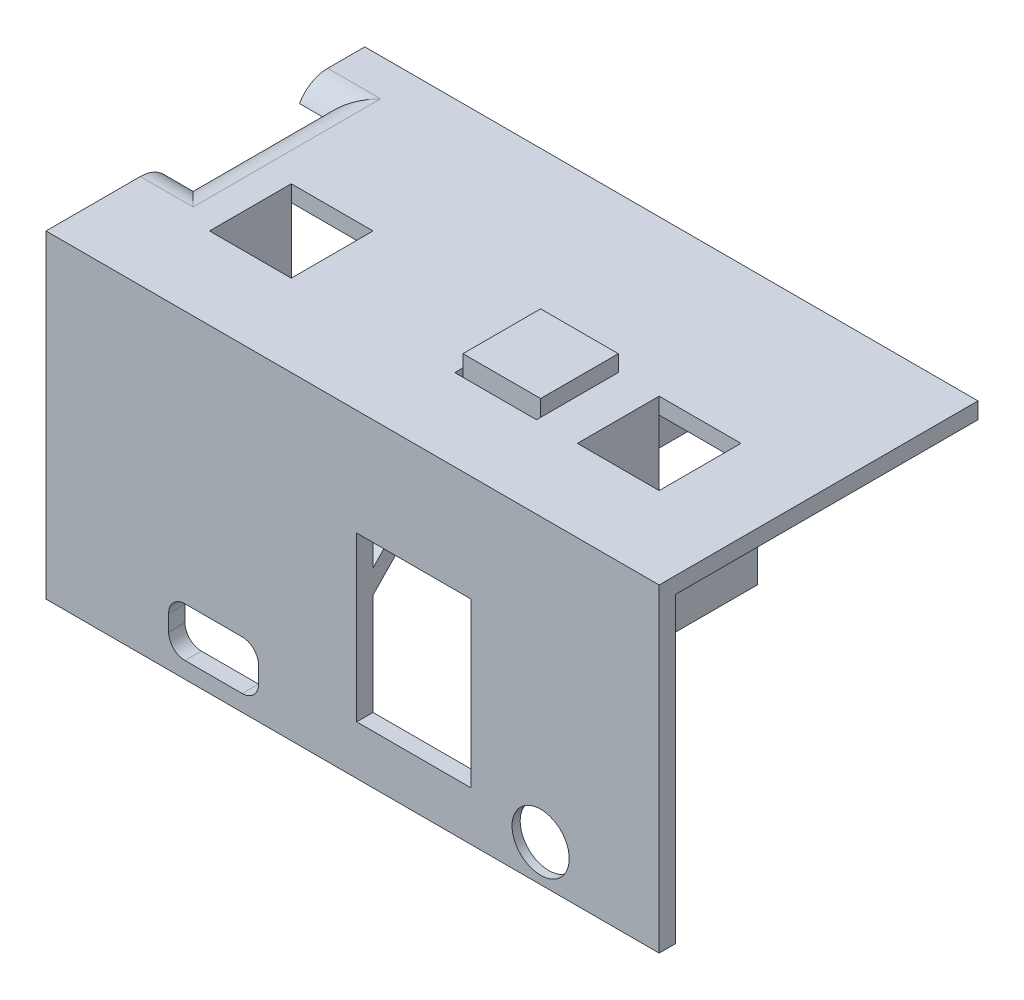
SolidWorks part; units mm, degrees
ref_plane "Front Plane" through (0, 0, 0) normal (0, 0, 1) x (1, 0, 0)
ref_plane "Top Plane" through (0, 0, 0) normal (0, 1, 0) x (1, 0, 0)
ref_plane "Right Plane" through (0, 0, 0) normal (1, 0, 0) x (0, 0, -1)
sketch "Sketch1" plane through (0, 0, 0) normal (0, 0, 1) x (1, 0, 0)
  line L1 (-37.5, 19.5) -> (37.5, 19.5)
  line L2 (-37.5, 19.5) -> (-37.5, -19.5)
  line L3 (-37.5, -19.5) -> (37.5, -19.5)
  line L4 (37.5, 19.5) -> (37.5, -19.5)
  point P4 (37.5, 0)
  point P6 (0, -19.5)
  dimension "D1" = 75
  dimension "D2" = 39
extrude "Boss-Extrude1" add sketch "Sketch1" along normal blind 2
sketch "Sketch2" plane through (0, 0, 0) normal (0, 0, -1) x (-1, 0, 0)
  line L0 (37.5, 19.5) -> (37.5, -19.5) construction
  line L1 (-37.5, 19.5) -> (37.5, 19.5)
  line L2 (-37.5, 19.5) -> (-37.5, 17.5)
  line L3 (-37.5, 17.5) -> (37.5, 17.5)
  line L4 (37.5, 19.5) -> (37.5, 17.5)
  dimension "D1" = 2
extrude "Boss-Extrude2" add sketch "Sketch2" along normal blind 38
sketch "Sketch4" plane through (0, 0, 2) normal (0, 0, 1) x (1, 0, 0)
  line L0 (37.5, -10.5) -> (28.5, -10.5) construction
  line L1 (37.5, -19.5) -> (37.5, 19.5) construction
  line L2 (28.5, -10.5) -> (28.5, -19.5) construction
  line L3 (-37.5, -19.5) -> (37.5, -19.5) construction
  line L4 (23, -19.5) -> (23, -15) construction
  line L5 (-37.5, 19.5) -> (-37.5, -19.5) construction
  line L6 (37.5, 19.5) -> (-37.5, 19.5) construction
  line L7 (-22.5, -11.5) -> (-11.5, -11.5)
  line L8 (-22.5, -11.5) -> (-22.5, -17.5)
  line L9 (-22.5, -17.5) -> (-11.5, -17.5)
  line L10 (-11.5, -11.5) -> (-11.5, -17.5)
  circle A0 centre (23, -15) radius 3.5
  circle A1 centre (23, 4.5) radius 2.25
  dimension "D5" = 7
  dimension "D10" = 4.5
  dimension "D1" = 9
  dimension "D2" = 9
  dimension "D3" = 4.5
  dimension "D4" = 14.5
  dimension "D6" = 15
  dimension "D7" = 49
  dimension "D8" = 2
  dimension "D9" = 6
  dimension "D11" = 15
extrude "Cut-Extrude1" cut sketch "Sketch4" against normal up to surface (2 mm away) up to face at (0, -1, 0)
sketch "Sketch6" plane through (0, 19.5, 0) normal (0, 1, 0) x (1, 0, 0)
  line L0 (37.5, -2) -> (37.5, 38) construction
  line L1 (2.5, 18) -> (12.5, 18)
  line L2 (2.5, 18) -> (2.5, 8)
  line L3 (2.5, 8) -> (12.5, 8)
  line L4 (12.5, 18) -> (12.5, 8)
  line L5 (17.5, 18) -> (27.5, 18)
  line L6 (17.5, 18) -> (17.5, 8)
  line L7 (17.5, 8) -> (27.5, 8)
  line L8 (27.5, 18) -> (27.5, 8)
  line L9 (37.5, -2) -> (-37.5, -2) construction
  line L10 (-37.5, -2) -> (-37.5, 38) construction
  line L11 (-27.5, 18) -> (-17.5, 18)
  line L12 (-27.5, 18) -> (-27.5, 8)
  line L13 (-27.5, 8) -> (-17.5, 8)
  line L14 (-17.5, 18) -> (-17.5, 8)
  dimension "D1" = 10
  dimension "D2" = 10
  dimension "D3" = 5
  dimension "D4" = 10
  dimension "D5" = 10
  dimension "D6" = 10
  dimension "D7" = 10
  dimension "D8" = 10
  dimension "D9" = 10
  dimension "D10" = 10
  dimension "D11" = 10
  dimension "D12" = 10
extrude "Cut-Extrude2" cut sketch "Sketch6" against normal up to surface (2 mm away) up to face at (0, 17.5, -19)
sketch "Sketch7" plane through (0, 17.5, 0) normal (0, -1, 0) x (1, 0, 0)
  line L0 (12.5, -18) -> (12.5, -8) construction
  line L2 (17.5, -8) -> (17.5, -18)
  line L3 (17.5, -18) -> (15.5, -18)
  line L4 (15.5, -8) -> (15.5, -18)
  line L6 (27.5, -8) -> (27.5, -18)
  line L7 (27.5, -18) -> (29.5, -18)
  line L8 (29.5, -8) -> (29.5, -18)
  line L9 (17.5, -8) -> (27.5, -8)
  line L10 (15.5, -8) -> (15.5, -6)
  line L11 (15.5, -6) -> (29.5, -6)
  line L12 (29.5, -8) -> (29.5, -6)
  line L14 (2.5, -8) -> (2.5, -18)
  line L15 (2.5, -18) -> (0.5, -18)
  line L16 (0.5, -8) -> (0.5, -18)
  line L17 (12.5, -18) -> (14.5, -18)
  line L18 (12.5, -18) -> (12.5, -8)
  line L20 (14.5, -18) -> (14.5, -8)
  line L22 (12.5, -8) -> (2.5, -8)
  line L23 (14.5, -8) -> (14.5, -6)
  line L24 (14.5, -6) -> (0.5, -6)
  line L25 (0.5, -8) -> (0.5, -6)
  line L27 (-17.5, -8) -> (-17.5, -18)
  line L28 (-17.5, -18) -> (-15.5, -18)
  line L29 (-15.5, -8) -> (-15.5, -18)
  line L30 (-27.5, -18) -> (-29.5, -18)
  line L31 (-27.5, -18) -> (-27.5, -8)
  line L33 (-29.5, -18) -> (-29.5, -8)
  line L34 (-27.5, -8) -> (-17.5, -8)
  line L35 (-29.5, -8) -> (-29.5, -6)
  line L36 (-29.5, -6) -> (-15.5, -6)
  line L37 (-15.5, -8) -> (-15.5, -6)
  dimension "D1" = 2
  dimension "D2" = 2
  dimension "D3" = 2
  dimension "D4" = 2
  dimension "D5" = 2
  dimension "D6" = 2
  dimension "D7" = 2
  dimension "D8" = 2
  dimension "D9" = 2
extrude "Boss-Extrude3" add sketch "Sketch7" along normal blind 10
sketch "Sketch8" plane through (0, 7.5, 0) normal (0, -1, 0) x (1, 0, 0)
  line L1 (-29.5, -6) -> (-15.5, -6)
  line L2 (-29.5, -6) -> (-29.5, -18)
  line L3 (-29.5, -18) -> (-15.5, -18)
  line L4 (-15.5, -6) -> (-15.5, -18)
  line L5 (0.5, -6) -> (14.5, -6)
  line L6 (0.5, -6) -> (0.5, -18)
  line L7 (0.5, -18) -> (14.5, -18)
  line L8 (14.5, -6) -> (14.5, -18)
  line L9 (15.5, -6) -> (29.5, -6)
  line L10 (15.5, -6) -> (15.5, -18)
  line L11 (15.5, -18) -> (29.5, -18)
  line L12 (29.5, -6) -> (29.5, -18)
extrude "Boss-Extrude4" add sketch "Sketch8" along normal blind 2
sketch "Sketch9" plane through (0, 17.5, 0) normal (0, -1, 0) x (1, 0, 0)
  line L1 (2.5, -18) -> (12.5, -18)
  line L5 (2.5, -8) -> (12.5, -8)
  line L6 (2.5, -8) -> (2.5, -18)
  line L7 (2.5, -18) -> (12.5, -18)
  line L8 (12.5, -8) -> (12.5, -18)
  line L12 (2.5, -18) -> (12.5, -18) construction
  line L13 (0.5, -6) -> (0.5, -18) construction
  line M10 (12.5, -18) -> (2.5, -18)
  dimension "D1" = 10
  dimension "D2" = 10
  dimension "D3" = 0
  dimension "D4" = 2
extrude "Boss-Extrude5" add sketch "Sketch9" against normal blind 4 separate body contours L8 L5 L6 M10
sketch "Sketch10" plane through (0, 17.5, 0) normal (0, -1, 0) x (1, 0, 0)
  line L19 (2.6, -8.1) -> (12.5, -8.1)
  line L21 (2.6, -8.1) -> (12.5, -8.1)
  line L22 (2.6, -8.1) -> (2.6, -18)
  line L23 (2.6, -18) -> (12.5, -18)
  line L24 (12.5, -8.1) -> (12.5, -18)
  line L25 (4.6, -10.1) -> (10.5, -10.1)
  line L26 (4.6, -10.1) -> (4.6, -16)
  line L27 (4.6, -16) -> (10.5, -16)
  line L28 (10.5, -10.1) -> (10.5, -16)
  line M3 (12.5, -18) -> (12.5, -8)
  line M6 (2.5, -18) -> (12.5, -18)
  dimension "D1" = 9.9
  dimension "D2" = 9.9
  dimension "D3" = 2
  dimension "D4" = 2
  dimension "D5" = 2
  dimension "D6" = 2
extrude "Boss-Extrude9" add sketch "Sketch10" along normal blind 2 contours L19 L22 L25 L28 L27 L26 M6 M3
sketch "Sketch11" plane through (0, 0, -18) normal (0, 0, -1) x (-1, 0, 0)
  line L0 (-12.5, 7.5) -> (-12.5, 17.5) construction
  line L1 (-2.6, 15.5) -> (-12.5, 15.5)
  line L2 (-2.6, 15.5) -> (-2.6, 17.35)
  line L3 (-2.6, 17.35) -> (-12.5, 17.35)
  line L4 (-12.5, 15.5) -> (-12.5, 17.35)
  dimension "D1" = 1.85
extrude "Boss-Extrude10" add sketch "Sketch11" along normal blind 4
sketch "Sketch12" plane through (0, 0, 0) normal (0, 0, -1) x (-1, 0, 0)
  circle A0 centre (-23, 4.5) radius 2.25
  circle A1 centre (-23, 4.5) radius 4.25
  dimension "D1" = 2
extrude "Boss-Extrude11" add sketch "Sketch12" along normal blind 2
sketch "Sketch16" plane through (0, 0, 0) normal (0, 0, -1) x (-1, 0, 0)
  line L0 (37.5, -19.5) -> (-23, -19.5) construction
  line L1 (11.5, -11.5) -> (22.5, -11.5)
  line L2 (11.5, -11.5) -> (11.5, -17.5)
  line L3 (11.5, -17.5) -> (22.5, -17.5)
  line L4 (22.5, -11.5) -> (22.5, -17.5)
  line L5 (10, -10) -> (24, -10)
  line L6 (10, -10) -> (10, -19.5)
  line L7 (10, -19.5) -> (24, -19.5)
  line L8 (24, -10) -> (24, -19.5)
  dimension "D1" = 1.5
  dimension "D2" = 1.5
  dimension "D3" = 1.5
extrude "Boss-Extrude13" add sketch "Sketch16" along normal blind 2
sketch "Sketch17" plane through (0, 17.5, 0) normal (0, -1, 0) x (1, 0, 0)
  line L0 (2.5, -8) -> (12.5, -8) construction
  line L1 (2.5, -18) -> (2.6, -18)
  line L2 (2.5, -18) -> (2.5, -8)
  line L3 (2.5, -8) -> (2.6, -8)
  line L4 (2.6, -18) -> (2.6, -8.1)
  line L6 (2.5, -8) -> (12.5, -8)
  line L7 (2.5, -8) -> (2.5, -8.1)
  line L8 (2.6, -8.1) -> (12.5, -8.1)
  line L9 (12.5, -8) -> (12.5, -8.1)
  line M7 (2.6, -18) -> (2.6, -8.1)
  line M8 (2.6, -8.1) -> (12.5, -8.1)
  line M9 (12.5, -8.1) -> (12.5, -8)
  line M10 (12.5, -8) -> (2.5, -8)
  line M11 (2.5, -8) -> (2.5, -18)
  line M12 (2.5, -18) -> (2.6, -18)
extrude "Cut-Extrude3" cut sketch "Sketch17" against normal through all contours L2 M12 M7 M8 M9 M10 M11
fillet "Fillet1" radius 2 4 edges at (-22.5, -17.5, 0) (-22.5, -11.5, 0) (-11.5, -17.5, 0) (-11.5, -11.5, 0)
fillet "Fillet2" radius 2 2 edges at (-24, -10, -1) (-10, -10, -1)
ref_plane "Plane1" through (0, 0, 0) normal (-1, 0, 0) x (0, 0, 1)
sketch "Sketch18" plane through (0, 0, 0) normal (-1, 0, 0) x (0, 0, 1)
  line L0 (-15.1663, 17.5) -> (0, 1.7996)
  line L5 (-17.9471, 17.5) -> (0, -1.079)
  line L6 (-38, 17.5) -> (0, 17.5) construction
  line L7 (0, 17.5) -> (0, -19.5) construction
  line L8 (-17.9471, 17.5) -> (-15.1663, 17.5)
  line L9 (0, -1.079) -> (0, 1.7996)
  dimension "D3" = 2
extrude "Boss-Extrude14" add sketch "Sketch18" along normal blind 2 and the other way blind 2
sketch "Sketch19" plane through (0, 0, 0) normal (0, 0, -1) x (-1, 0, 0)
  line L1 (-14.5, 6.5) -> (-0.5, 6.5)
  line L2 (-14.5, 6.5) -> (-14.5, -13.5)
  line L3 (-14.5, -13.5) -> (-0.5, -13.5)
  line L4 (-0.5, 6.5) -> (-0.5, -13.5)
  line L5 (10, -19.5) -> (-37.5, -19.5) construction
  line L6 (-37.5, -19.5) -> (-37.5, 17.5) construction
  dimension "D1" = 14
  dimension "D2" = 20
  dimension "D3" = 6
  dimension "D4" = 23
extrude "Cut-Extrude4" cut sketch "Sketch19" against normal blind 10 and the other way blind 7
sketch "Sketch22" plane through (0, 0, -38) normal (0, 0, -1) x (-1, 0, 0)
  line L0 (37.5, 19.5) -> (-37.5, 19.5) construction
  line L1 (-29.5, 5.5) -> (-15.5, 5.5)
  line L2 (-29.5, 5.5) -> (-29.5, 19.5)
  line L3 (-29.5, 19.5) -> (-15.5, 19.5)
  line L4 (-15.5, 5.5) -> (-15.5, 19.5)
  line L5 (37.5, 17.5) -> (37.5, -19.5) construction
  line L6 (29.5, 5.5) -> (15.5, 5.5)
  line L7 (29.5, 5.5) -> (29.5, 19.5)
  line L8 (29.5, 19.5) -> (15.5, 19.5)
  line L9 (15.5, 5.5) -> (15.5, 19.5)
  line L10 (-37.5, -19.5) -> (-37.5, 17.5) construction
  dimension "D1" = 14
  dimension "D2" = 14
  dimension "D3" = 8
  dimension "D4" = 8
  dimension "D5" = 14
extrude "Boss-Extrude15" add sketch "Sketch22" against normal blind 3
fillet "Fillet3" radius 7 4 edges at (-29.5, 5.5, -36.5) (-15.5, 5.5, -36.5) (15.5, 5.5, -36.5) (29.5, 5.5, -36.5)
sketch "Sketch23" plane through (0, 0, -38) normal (0, 0, -1) x (-1, 0, 0)
  circle A0 centre (-22.5, 12.5) radius 3.05
  circle A1 centre (22.5, 12.5) radius 3.05
  dimension "D1" = 6.1
  dimension "D2" = 6.1
extrude "Cut-Extrude6" cut sketch "Sketch23" against normal blind 4
sketch "Sketch24" plane through (0, 5.5, 0) normal (0, -1, 0) x (1, 0, 0)
  line L1 (15.5, -6) -> (14.5, -6)
  line L2 (15.5, -6) -> (15.5, -18)
  line L3 (15.5, -18) -> (14.5, -18)
  line L4 (14.5, -6) -> (14.5, -18)
extrude "Boss-Extrude16" add sketch "Sketch24" against normal up to surface (12 mm away) up to face at (0, 17.5, -30.6667)
sketch "Sketch25" plane through (0, 0, -2) normal (0, 0, -1) x (-1, 0, 0)
  line L0 (-31.1594, -19.4878) -> (-14.8406, -19.4878)
  line L1 (10, -19.5) -> (24, -19.5)
  line L2 (10, -19.5) -> (10, -9.8075)
  line L3 (10, -9.8075) -> (24, -9.8075)
  line L4 (24, -19.5) -> (24, -9.8075)
  line L5 (-31.1594, -19.4878) -> (-31.1594, -10.5122)
  line L6 (-14.8406, -19.4878) -> (-14.8406, -10.5122)
  line L7 (-31.1594, -10.5122) -> (-14.8406, -10.5122)
  line L8 (-31.1594, -19.4878) -> (-14.8406, -10.5122) construction
  line L9 (-14.8406, -19.4878) -> (-31.1594, -10.5122) construction
  point P6 (-23, -15)
extrude "Cut-Extrude7" cut sketch "Sketch25" against normal blind 2
sketch "Sketch26" plane through (0, 0, -2) normal (0, 0, -1) x (-1, 0, 0)
  circle A0 centre (-23, 4.5) radius 4.25
extrude "Cut-Extrude8" cut sketch "Sketch26" against normal up to surface (2 mm away) up to face at (0, -1, 0)
sketch "Sketch27" plane through (0, 0, 2) normal (0, 0, 1) x (1, 0, 0)
  circle A0 centre (23, 4.5) radius 2.25
extrude "Boss-Extrude17" add sketch "Sketch27" along a picked direction on the side against the normal up to surface (2 mm away)
sketch "Sketch28" plane through (0, 0, -38) normal (0, 0, -1) x (-1, 0, 0)
  line L1 (-42.4925, 24.9847) -> (43.0335, 24.9847)
  line L2 (-42.4925, 24.9847) -> (-42.4925, -1.8022)
  line L3 (-42.4925, -1.8022) -> (43.0335, -1.8022)
  line L4 (43.0335, 24.9847) -> (43.0335, -1.8022)
extrude "Cut-Extrude9" cut sketch "Sketch28" against normal blind 1
sketch "Sketch29" plane through (0, 0, -35) normal (0, 0, 1) x (1, 0, 0)
  line L1 (15.5, 17.5) -> (29.5, 17.5)
  line L2 (15.5, 17.5) -> (15.5, 12.5)
  line L4 (29.5, 17.5) -> (29.5, 12.5)
  arc A0 (15.5, 12.5) -> (29.5, 12.5) centre (22.5, 12.5) ccw
extrude "Boss-Extrude18" add sketch "Sketch29" along normal blind 1
mirror "Mirror1" about plane through (0, 0, 0) normal (-1, 0, 0) of "Boss-Extrude18"
sketch "Sketch30" plane through (0, 21.5, 0) normal (0, 1, 0) x (1, 0, 0)
  line L0 (2.5, 8) -> (12.5, 8) construction
  line L1 (2.5, 18) -> (3, 18)
  line L2 (2.5, 18) -> (2.5, 8)
  line L4 (3, 18) -> (3, 8.5)
  line L6 (12.5, 8) -> (2.5, 8)
  line L7 (12.5, 8) -> (12.5, 8.5)
  line L8 (12.5, 8.5) -> (3, 8.5)
  dimension "D1" = 0.5
  dimension "D2" = 0.5
extrude "Cut-Extrude10" cut sketch "Sketch30" against normal blind 10
sketch "Sketch31" plane through (0, 0, 0) normal (0, 0, -1) x (-1, 0, 0)
  line L0 (37.5, -19.5) -> (-37.5, -19.5) construction
  line L1 (-32, -10.5) -> (-17, -10.5)
  line L2 (-32, -10.5) -> (-32, -19.5)
  line L3 (-32, -19.5) -> (-17, -19.5)
  line L4 (-17, -10.5) -> (-17, -19.5)
  circle A0 centre (-23, -15) radius 3.5 construction
  circle A1 centre (-23, -15) radius 3.5
  dimension "D3" = 6
  dimension "D4" = 7
  dimension "D1" = 15
  dimension "D2" = 9
extrude "Cut-Extrude11" cut sketch "Sketch31" against normal blind 1
sketch "Sketch32" plane through (0, 17.5, 0) normal (0, -1, 0) x (1, 0, 0)
  line L0 (-37.5, -37) -> (37.5, -37) construction
  line L1 (-10, -24) -> (10, -24)
  line L2 (-10, -24) -> (-10, -32)
  line L3 (-10, -32) -> (10, -32)
  line L4 (10, -24) -> (10, -32)
  point P8 (0, -37)
  point P9 (0, -32)
  dimension "D1" = 20
  dimension "D2" = 8
  dimension "D3" = 5
extrude "Cut-Extrude12" cut sketch "Sketch32" against normal blind 1
sketch "Sketch33" plane through (0, 6.5, 0) normal (0, -1, 0) x (1, 0, 0)
  line L0 (0.5, -7) -> (0.5, -4.5405) construction
  line L1 (14.5, -7) -> (0.5, -7)
  line L2 (14.5, -7) -> (14.5, -5.7703)
  line L3 (14.5, -5.7703) -> (0.5, -5.7703)
  line L4 (0.5, -7) -> (0.5, -5.7703)
sketch "Sketch34" plane through (0, 5.5, 0) normal (0, -1, 0) x (1, 0, 0)
  line L0 (0.5, -7) -> (0.5, -4.5405) construction
  line L1 (14.5, -7) -> (0.5, -7)
  line L2 (14.5, -7) -> (14.5, -6)
  line L3 (14.5, -6) -> (0.5, -6)
  line L4 (0.5, -7) -> (0.5, -6)
  line L5 (29.5, -6) -> (0.5, -6) construction
extrude "Boss-Extrude19" add sketch "Sketch34" along normal up to surface (1 mm away)
sketch "Sketch35" plane through (0, 19.5, 0) normal (0, 1, 0) x (1, 0, 0)
  line L0 (-37.5, -2) -> (-37.5, 37) construction
  line L1 (-37.5, 29) -> (-34.5, 29)
  line L2 (-37.5, 29) -> (-37.5, 13)
  line L3 (-37.5, 13) -> (-34.5, 13)
  line L4 (-34.5, 29) -> (-34.5, 13)
  line L5 (-37.5, 37) -> (37.5, 37) construction
  dimension "D1" = 16
  dimension "D2" = 3
  dimension "D3" = 8
extrude "Cut-Extrude13" cut sketch "Sketch35" against normal through all
fillet "Fillet4" radius 4 3 edges at (-36, 19.5, -13) (-36, 19.5, -29) (-34.5, 19.5, -21)
sketch "Sketch36" plane through (0, 15.5, 0) normal (0, -1, 0) x (1, 0, 0)
  line L0 (12.5, -22) -> (2.6, -22) construction
  line L1 (3, -18) -> (2.6, -18)
  line L2 (3, -18) -> (3, -22)
  line L3 (3, -22) -> (2.6, -22)
  line L4 (2.6, -18) -> (2.6, -22)
  line L5 (2.6, -18) -> (2.6, -22) construction
extrude "Cut-Extrude14" cut sketch "Sketch36" against normal blind 10
sketch "Sketch37" plane through (0, 17.5, 0) normal (0, -1, 0) x (1, 0, 0)
  line L0 (-10, -32) -> (-10, -33)
  line L1 (-10, -24) -> (10, -24)
  line L3 (-10, -32) -> (10, -32)
  line L4 (10, -24) -> (10, -32)
  line L5 (-10, -23) -> (12, -23)
  line L6 (-10, -23) -> (-10, -24)
  line L7 (-10, -33) -> (12, -33)
  line L8 (12, -23) -> (12, -33)
  dimension "D1" = 1
  dimension "D2" = 1
  dimension "D3" = 2
extrude "Boss-Extrude20" add sketch "Sketch37" along normal blind 7 separate body
sketch "Sketch38" plane through (0, 10.5, 0) normal (0, -1, 0) x (1, 0, 0)
  line L1 (-10, -23) -> (12, -23)
  line L2 (-10, -23) -> (-10, -33)
  line L3 (-10, -33) -> (12, -33)
  line L4 (12, -23) -> (12, -33)
extrude "Boss-Extrude21" add sketch "Sketch38" along normal blind 2
